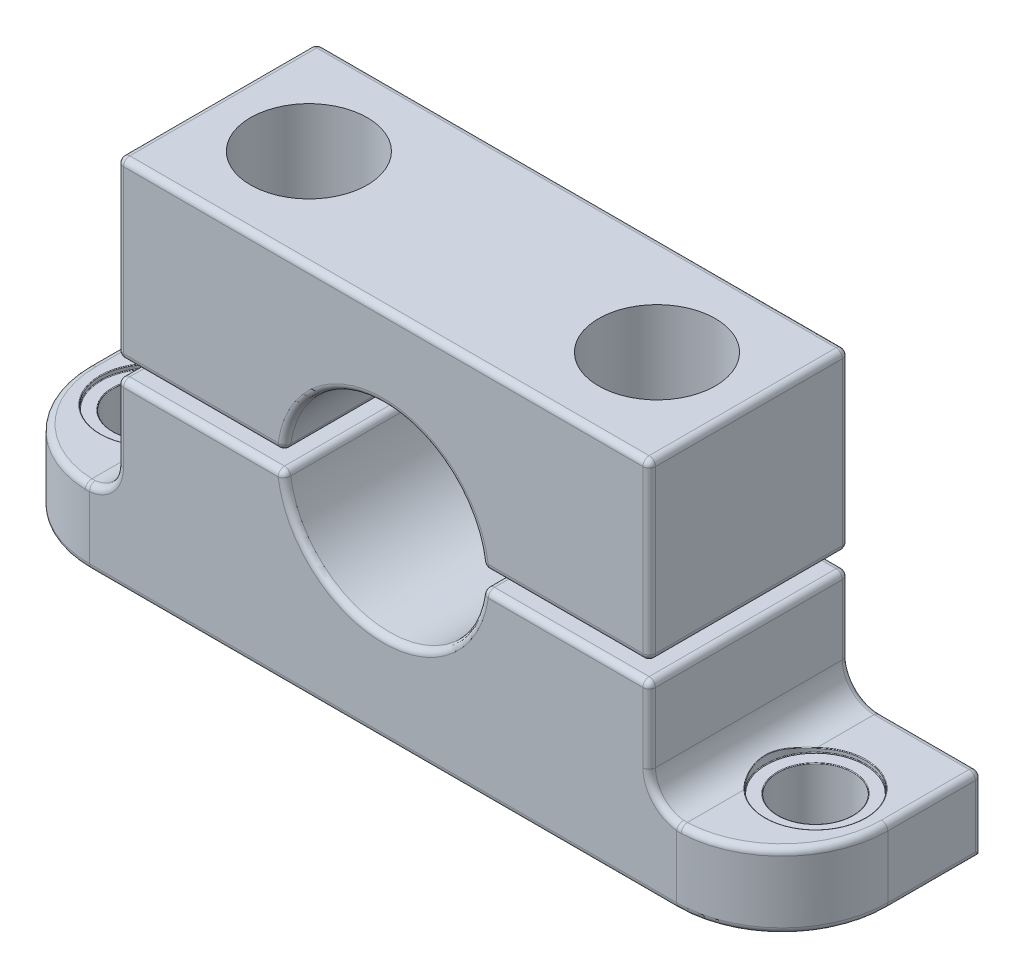
SolidWorks part; units mm, degrees
note: '?' marks a value the reader was unsure of.
material "ABS"
ref_plane "Front" through (0, 0, 0) normal (0, 0, 1) x (1, 0, 0)
ref_plane "Top" through (0, 0, 0) normal (0, 1, 0) x (1, 0, 0)
ref_plane "Right" through (0, 0, 0) normal (1, 0, 0) x (0, 0, -1)
sketch "Sketch1" plane through (0, 0, 0) normal (0, 0, 1) x (1, 0, 0)
  line L0 (0, 22.46) -> (0, 0) construction
  line L1 (-24, 0) -> (24, 0) construction
  line L2 (0, 0) -> (0, 11.46) construction
  line L3 (-20, 0) -> (20, 0) construction
  line L4 (17.75, 0) -> (22.25, 0) construction
  line L5 (22.25, 0) -> (22.25, 1.27) construction
  line L6 (17.75, 0) -> (17.75, 1.27) construction
  line L7 (-17.75, 0) -> (-17.75, 1.27) construction
  line L8 (-22.25, 0) -> (-22.25, 1.27) construction
  line L9 (-17.75, 0) -> (-22.25, 0) construction
  line L10 (-16, 11.46) -> (16, 11.46) construction
  line L11 (-16, 10.952) -> (16, 10.952) construction
  line L12 (-16, 11.968) -> (16, 11.968) construction
  line L13 (17.369, 0) -> (17.369, 1.27) construction
  line L14 (22.631, 0) -> (22.631, 1.27) construction
  line L15 (-17.369, 0) -> (-17.369, 1.27) construction
  line L16 (-22.631, 0) -> (-22.631, 1.27) construction
  line L17 (-11.0713, 10.952) -> (11.0713, 10.952) construction
  line L18 (-11.0713, 11.968) -> (11.0713, 11.968) construction
  line L19 (-11.0713, 11.46) -> (11.0713, 11.46) construction
  line L20 (-24, 0) -> (-24, 4.492) construction
  line L21 (-24, 4.492) -> (-16, 4.492) construction
  line L22 (-16, 10.952) -> (-16, 4.492) construction
  line L23 (-16, 11.968) -> (-16, 22.46) construction
  line L24 (-16, 22.46) -> (16, 22.46) construction
  line L25 (24, 0) -> (24, 4.492) construction
  line L26 (24, 4.492) -> (16, 4.492) construction
  line L27 (16, 10.952) -> (16, 4.492) construction
  line L28 (16, 11.968) -> (16, 22.46) construction
  line L29 (0, 22.46) -> (0, 15.46) construction
  line L30 (0.3175, 15.46) -> (-0.3175, 15.46) construction
  line L31 (16, 4.492) -> (16, 0) construction
  circle A0 centre (0, 11.46) radius 6 construction
  arc A1 (-17.905, 4.492) -> (-16, 6.397) centre (-17.905, 6.397) ccw construction
  arc A2 (17.905, 4.492) -> (16, 6.397) centre (17.905, 6.397) cw construction
  point P5 (0, 0)
  point P9 (0, 11.46)
  point P11 (0, 0)
  point P12 (20, 0)
  point P13 (-20, 0)
  point P16 (20, 0)
  point P37 (0, 10.952)
  point P40 (0, 11.968)
  point P60 (0, 15.46)
  point P64 (20, 4.492)
  dimension "D1" = 1.27
  dimension "D8" = 4.492
  dimension "D12" = 0.635
  dimension "D10" = 1.905
  dimension "D11" = 1.905
  dimension "D9" = 4
  dimension "D13" = 4
  dimension "D2" = 0.508
  dimension "D3" = 0.508
  dimension "D4" = 0.381
  dimension "D5" = 0.381
  dimension "D6" = 0.381
  dimension "D7" = 0.381
sketch "Sketch3" plane through (0, 0, 0) normal (0, 0, 1) x (1, 0, 0)
  line L0 (-16, 22.46) -> (16, 22.46) construction
  line L1 (16, 11.968) -> (16, 22.46) construction
  line L2 (-16, 11.968) -> (16, 11.968) construction
  line L3 (-16, 11.968) -> (-16, 22.46) construction
  line L4 (-16, 10.952) -> (-16, 4.492) construction
  line L5 (-24, 4.492) -> (-16, 4.492) construction
  line L6 (-24, 0) -> (-24, 4.492) construction
  line L7 (-24, 0) -> (24, 0) construction
  line L8 (24, 0) -> (24, 4.492) construction
  line L9 (24, 4.492) -> (16, 4.492) construction
  line L10 (16, 10.952) -> (16, 4.492) construction
  line L11 (-16, 10.952) -> (16, 10.952) construction
  line L12 (-16, 22.46) -> (16, 22.46)
  line L13 (16, 11.968) -> (16, 22.46)
  line L14 (-16, 11.968) -> (-5.9785, 11.968)
  line L15 (-16, 11.968) -> (-16, 22.46)
  line L16 (-16, 10.952) -> (-16, 6.397)
  line L17 (-24, 4.492) -> (-17.905, 4.492)
  line L18 (-24, 0) -> (-24, 4.492)
  line L19 (-24, 0) -> (24, 0)
  line L20 (24, 0) -> (24, 4.492)
  line L21 (24, 4.492) -> (17.905, 4.492)
  line L22 (16, 10.952) -> (16, 6.397)
  line L23 (-16, 10.952) -> (-5.9785, 10.952)
  line L24 (5.9785, 11.968) -> (16, 11.968)
  line L25 (5.9785, 10.952) -> (16, 10.952)
  arc A0 (-17.905, 4.492) -> (-16, 6.397) centre (-17.905, 6.397) ccw construction
  arc A1 (16, 6.397) -> (17.905, 4.492) centre (17.905, 6.397) ccw construction
  circle A2 centre (0, 11.46) radius 6 construction
  arc A3 (-17.905, 4.492) -> (-16, 6.397) centre (-17.905, 6.397) ccw
  arc A4 (16, 6.397) -> (17.905, 4.492) centre (17.905, 6.397) ccw
  arc A5 (5.9785, 11.968) -> (-5.9785, 11.968) centre (0, 11.46) ccw
  arc A6 (-5.9785, 10.952) -> (5.9785, 10.952) centre (0, 11.46) ccw
extrude "Boss-Extrude1" add sketch "Sketch3" against normal blind 12
sketch "Sketch4" plane through (0, 0, 0) normal (0, -1, 0) x (1, 0, 0)
  line L0 (-24, 0) -> (-24, -12) construction
  line L1 (-24, 0) -> (-16, 0) construction
  line L2 (-24, -6) -> (24, -6) construction
  line L3 (24, -12) -> (24, 0) construction
  line L4 (-20, 0) -> (-20, -12) construction
  line L5 (20, 0) -> (20, -12) construction
  line L6 (-24, -12) -> (24, -12) construction
  line L7 (0, 0) -> (0, -12) construction
  circle A0 centre (-20, -6) radius 2.25
  circle A1 centre (20, -6) radius 2.25
  point P7 (-24, -6)
  dimension "D1" = 4.5
extrude "Cut-Extrude1" cut sketch "Sketch4" against normal through all
sketch "Sketch6" plane through (0, 4.492, 0) normal (0, 1, 0) x (1, 0, 0)
  line L0 (0, 0) -> (0, 12) construction
  line L1 (-24, 0) -> (24, 0) construction
  line L2 (16, 12) -> (-16, 12) construction
  circle A1 centre (-20, 6) radius 2.25 construction
  circle A2 centre (-20, 6) radius 2.25
  circle A4 centre (-20, 6) radius 2.631
  circle A5 centre (20, 6) radius 2.631
  dimension "D1" = 0.381
sketch "Sketch7" plane through (0, 0, 0) normal (0, 0, 1) x (1, 0, 0)
  line L0 (-24, 4.238) -> (24, 4.238) construction
  line L1 (-16, 10.952) -> (-16, 0) construction
  line L2 (-24, 0) -> (24, 0) construction
  line L3 (16, 10.952) -> (16, 0) construction
  line L5 (-24, 0) -> (-24, 4.492) construction
  line L6 (-24, 4.492) -> (-16, 4.492) construction
  line L7 (24, 0) -> (24, 4.492) construction
  line L8 (-20, 4.492) -> (-20, 4.238) construction
  line L9 (20, 4.492) -> (20, 4.238) construction
  line L10 (24, 4.492) -> (16, 4.492) construction
  dimension "D1" = 0.254
sketch "Sketch8" plane through (0, 10.952, 0) normal (0, 1, 0) x (1, 0, 0)
  line L0 (0, 0) -> (0, 12) construction
  line L1 (16, 12) -> (-16, 12) construction
  circle A0 centre (-20, 6) radius 2.631 construction
  circle A1 centre (20, 6) radius 2.631 construction
  circle A2 centre (-20, 6) radius 2.631 construction
  circle A3 centre (20, 6) radius 2.631 construction
  circle A4 centre (-20, 6) radius 3.012
  circle A5 centre (20, 6) radius 3.012
  dimension "D1" = 0.381
extrude "Cut-Extrude3" cut sketch "Sketch8" against normal up to vertex (6.714 mm away) up to point (-20, 4.238, 0)
sketch "Sketch10" plane through (0, 22.46, 0) normal (0, 1, 0) x (1, 0, 0)
  line L0 (-16, 12) -> (-16, 0) construction
  line L1 (16, 12) -> (16, 0) construction
  line L2 (-16, 12) -> (-16, 0) construction
  line L3 (16, 12) -> (16, 0) construction
  line L4 (-13.968, 12) -> (-13.968, 0) construction
  line L5 (0, 0) -> (0, 12) construction
  line L6 (13.968, 12) -> (13.968, 0) construction
  circle A0 centre (-10.468, 6) radius 2 construction
  circle A1 centre (10.468, 6) radius 2.254
  circle A2 centre (-10.468, 6) radius 2.254
  circle A3 centre (10.468, 6) radius 2 construction
  circle A4 centre (-10.468, 6) radius 3.5 construction
  circle A5 centre (10.468, 6) radius 3.5 construction
  dimension "D1" = 2.032
  dimension "D3" = 0.254
extrude "Cut-Extrude4" cut sketch "Sketch10" against normal through all
ref_plane "Plane1" through (0, 0, -6) normal (0, 0, 1) x (1, 0, 0)
sketch "Sketch12" plane through (0, 22.46, 0) normal (0, 1, 0) x (1, 0, 0)
  line L0 (0, 12) -> (0, 0) construction
  circle A0 centre (-10.468, 6) radius 3.3855 construction
  circle A1 centre (10.468, 6) radius 3.5125
  circle A2 centre (-10.468, 6) radius 3.5125
  circle A3 centre (10.468, 6) radius 3.3855 construction
  dimension "D2" = 7.025
extrude "Cut-Extrude5" cut sketch "Sketch12" against normal blind 7.015
sketch "Sketch13" plane through (0, 0, 0) normal (0, 1, 0) x (1, 0, 0)
  line L0 (-10.468, 12) -> (-10.468, 0) construction
  line L1 (16, 12) -> (-16, 12) construction
  line L2 (0, 12) -> (0, 0) construction
  line L3 (10.468, 12) -> (10.468, 0) construction
  circle A0 centre (-10.468, 6) radius 2.0066 construction
  point P2 (-10.468, 6)
  point P9 (-10.468, 12)
  point P10 (-10.468, 0)
  point P17 (10.468, 12)
  point P18 (10.468, 0)
sketch "Sketch15" plane through (0, 0, -6) normal (0, 0, 1) x (1, 0, 0)
  line L0 (-10.468, 4.238) -> (-10.468, 22.46) construction
  line L1 (-10.468, 22.46) -> (-13.968, 22.46) construction
  line L2 (-13.968, 22.46) -> (-13.968, 15.46) construction
  line L3 (-13.968, 15.46) -> (-12.468, 15.46) construction
  line L4 (-12.468, 15.46) -> (-12.468, 4.238) construction
  line L5 (-12.468, 4.238) -> (-10.468, 4.238) construction
  line L6 (-24, 4.238) -> (24, 4.238) construction
  line L8 (-16, 22.46) -> (16, 22.46) construction
  line L9 (-10.468, 4.238) -> (-10.468, 22.46)
  line L10 (-10.468, 22.46) -> (-13.968, 22.46)
  line L11 (-13.968, 22.46) -> (-13.968, 15.46)
  line L12 (-13.968, 15.46) -> (-12.468, 15.46)
  line L13 (-12.468, 15.46) -> (-12.468, 4.238)
  line L14 (-12.468, 4.238) -> (-10.468, 4.238)
  dimension "D2" = 3.5
  dimension "D1" = 7
  dimension "D3" = 2
revolve "Revolve1" [suppressed] add sketch "Sketch15" angle 360 about L9
chamfer "Chamfer1" [suppressed] distance 0.127 angle 45
sketch "Sketch16" [suppressed] plane through (0, 25, 0) normal (0, 1, 0) x (1, 0, 0)
  line L0 (-10.468, 12) -> (-10.468, 0) construction
  line L1 (-10.468, 7.7321) -> (-11.968, 6.866)
  line L2 (-11.968, 6.866) -> (-11.968, 5.134)
  line L3 (-11.968, 5.134) -> (-10.468, 4.2679)
  line L4 (-10.468, 4.2679) -> (-8.968, 5.134)
  line L5 (-8.968, 5.134) -> (-8.968, 6.866)
  line L6 (-8.968, 6.866) -> (-10.468, 7.7321)
  circle A0 centre (-10.468, 6) radius 1.5 construction
  dimension "Hex Size" = 3
extrude "Cut-Extrude6" [suppressed] cut sketch "Sketch16" against normal blind 2.31
mirror "Mirror1" [suppressed] about plane through (0, 0, 0) normal (1, 0, 0)
fillet "Fillet1" radius 0.381 18 edges at (0, 22.46, -12) (-16, 22.46, -6) (-16, 17.214, -12) (-16, 17.214, 0) (16, 17.214, -12) (16, 22.46, -6) (16, 17.214, 0) (0, 22.46, 0) (16, 11.968, -6) (10.9892, 11.968, -12) (-10.9892, 11.968, -12) (-16, 11.968, -6) (-10.9892, 11.968, 0) (10.9892, 11.968, 0) (0, 17.46, -12) (0, 17.46, 0) (5.9785, 11.968, -6) (-5.9785, 11.968, -6)
fillet "Fillet4" radius 6.35 2 edges at (24, 2.246, 0) (-24, 2.246, 0)
fillet "Fillet2" radius 0.381 33 edges at (20.9525, 4.492, -12) (16.558, 5.05, -12) (16, 8.6745, 0) (16.4706, 5.1434, 0) (-16.4706, 5.1434, 0) (-20.9525, 4.492, -12) (-16.558, 5.05, -12) (16, 8.6745, -12) (24, 0, -9.175) (24, 2.246, -12) (24, 4.492, -9.175) (0, 0, 0) (-24, 2.246, -12) (-24, 0, -9.175) (-24, 4.492, -9.175) (-16, 8.6745, 0) (-16, 8.6745, -12) (16, 10.952, -6) (-16, 10.952, -6) (-10.9892, 10.952, 0) (10.9892, 10.952, 0) (10.9892, 10.952, -12) (-10.9892, 10.952, -12) (0, 5.46, -12) (0, 5.46, 0) (5.9785, 10.952, -6) (-5.9785, 10.952, -6) (22.2294, 4.492, -1.951) (22.1401, 0, -1.8599) (-22.1401, 0, -1.8599) (-22.2294, 4.492, -1.951)
fillet "Fillet3" radius 0.0381 8 edges at (-23.012, 4.238, -6) (23.012, 4.238, -6) (23.012, 4.492, -6) (17.1034, 4.6688, -6.8258) (22.25, 4.238, -6) (-17.0187, 4.7107, -5.5707) (-23.012, 4.492, -6) (-22.25, 4.238, -6)
sketch "Sketch17" plane through (0, 0, 0) normal (0, 0, 1) x (1, 0, 0)
  line L0 (0, 22.46) -> (0, 0) construction
  line L1 (-15.619, 22.46) -> (15.619, 22.46) construction
  line L2 (-16, 11.23) -> (16, 11.23) construction
  line L3 (-16, 6.397) -> (-16, 10.571) construction
  line L4 (16, 10.571) -> (16, 6.397) construction
  point P7 (0, 11.23)
ref_axis "Center Axis 1" through (0, 11.46, -11.619) along (0, 0, 1)?
ref_plane "Split Plane" through (0, 11.46, 0) normal (0, 1, 0) x (1, 0, 0)
ref_plane "Center Plane" through (0, 0, -6) normal (0, 0, 1) x (1, 0, 0)
ref_point "Origin Base"
split "Split1" trim tools "Split Plane" bodies to split 117 118 resulting bodies 132 133
equation "\"D8@Sketch1\"=\"Oall Ht@Sketch1\"*.20"
equation "\"D1@Sketch4\"= \"HoldDia@Sketch1\""
equation "\"D1@Cut-Extrude5\"=\"HeadDp@Sketch1\"+.015"
equation "\"D1@Sketch15\"=\"HeadDp@Sketch1\""
equation "\"D3@Sketch15\"=\"ThrdDia@Sketch10\"*.5"
equation "\"D1@Cut-Extrude6\"= \"HeadDp@Sketch1\"*.33"
equation "\"D2@Sketch12\"=\"Head Dia@Sketch10\"+.025"
equation "\"D2@Sketch15\"=\"Head Dia@Sketch10\"*.50"
equation "\"D13@Sketch1\"=\"D9@Sketch1\""
